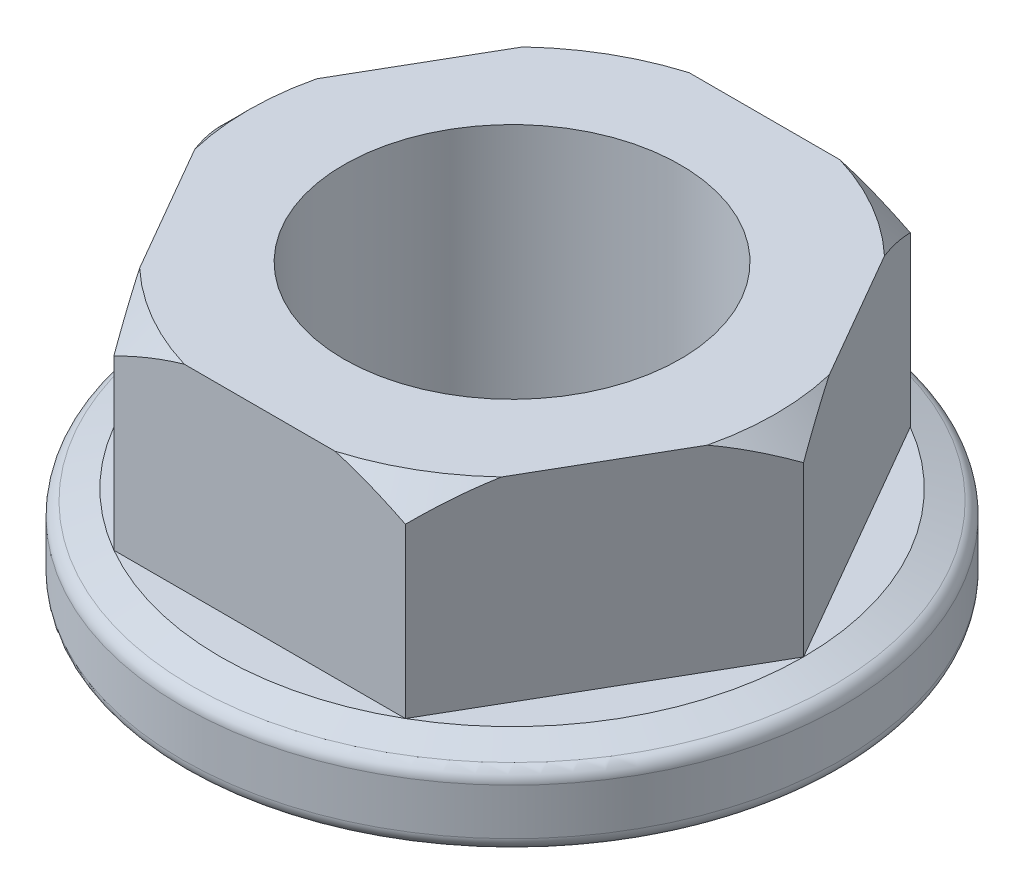
SolidWorks part; units mm, degrees
material "AISI 1045 Steel, cold drawn"
ref_plane "Front Plane" through (0, 0, 0) normal (0, 0, 1) x (1, 0, 0)
ref_plane "Top Plane" through (0, 0, 0) normal (0, 1, 0) x (1, 0, 0)
ref_plane "Right Plane" through (0, 0, 0) normal (1, 0, 0) x (0, 0, -1)
sketch "Sketch1" plane through (0, 0, 0) normal (0, 1, 0) x (1, 0, 0)
  line L1 (10.3923, 0) -> (5.1962, 9)
  line L2 (5.1962, 9) -> (-5.1962, 9)
  line L3 (-5.1962, 9) -> (-10.3923, 0)
  line L4 (-10.3923, 0) -> (-5.1962, -9)
  line L5 (-5.1962, -9) -> (5.1962, -9)
  line L6 (5.1962, -9) -> (10.3923, 0)
  circle A0 centre (0, 0) radius 9 construction
  circle A1 centre (0, 0) radius 6
  dimension "D2" = 12
  dimension "D1" = 18
extrude "Boss-Extrude1" add sketch "Sketch1" along normal blind 10
sketch "Sketch2" plane through (0, 0, 0) normal (0, -1, 0) x (1, 0, 0)
  line L1 (10.3923, 0) -> (5.1962, 9)
  line L2 (5.1962, 9) -> (-5.1962, 9)
  line L3 (-5.1962, 9) -> (-10.3923, 0)
  line L4 (-10.3923, 0) -> (-5.1962, -9)
  line L5 (-5.1962, -9) -> (5.1962, -9)
  line L6 (5.1962, -9) -> (10.3923, 0)
  circle A0 centre (0, 0) radius 11.75
  circle A1 centre (0, 0) radius 9 construction
  dimension "D1" = 23.5
extrude "Boss-Extrude2" add sketch "Sketch2" against normal blind 3
sketch "Sketch3" plane through (0, 0, 0) normal (0, 0, 1) x (1, 0, 0)
  line L0 (-10.3923, 9) -> (-9.3923, 10)
  line L1 (-10.3923, 9) -> (-10.3923, 10)
  line L2 (-10.3923, 10) -> (-9.3923, 10)
  line L5 (-10.3923, 10) -> (-10.3923, 3) construction
  line L6 (-10.3923, 3) -> (-11.75, 2.5)
  line L7 (11.75, 3) -> (-11.75, 3) construction
  line L8 (-11.75, 3) -> (-11.75, 0) construction
  line L9 (-11.75, 2.5) -> (-11.75, 3)
  line L10 (-11.75, 3) -> (-10.3923, 3)
  line L11 (0, 0) -> (0, 50000) construction
  line L12 (-11.75, 0) -> (11.75, 0) construction
  point P10 (0, 0)
  dimension "D1" = 1
  dimension "D2" = 0.5
revolve "Cut-Revolve1" cut sketch "Sketch3" angle 360 about L11
fillet "Fillet1" radius 0.5 2 edges at (0, 0, -11.75) (0, 2.5, -11.75)
